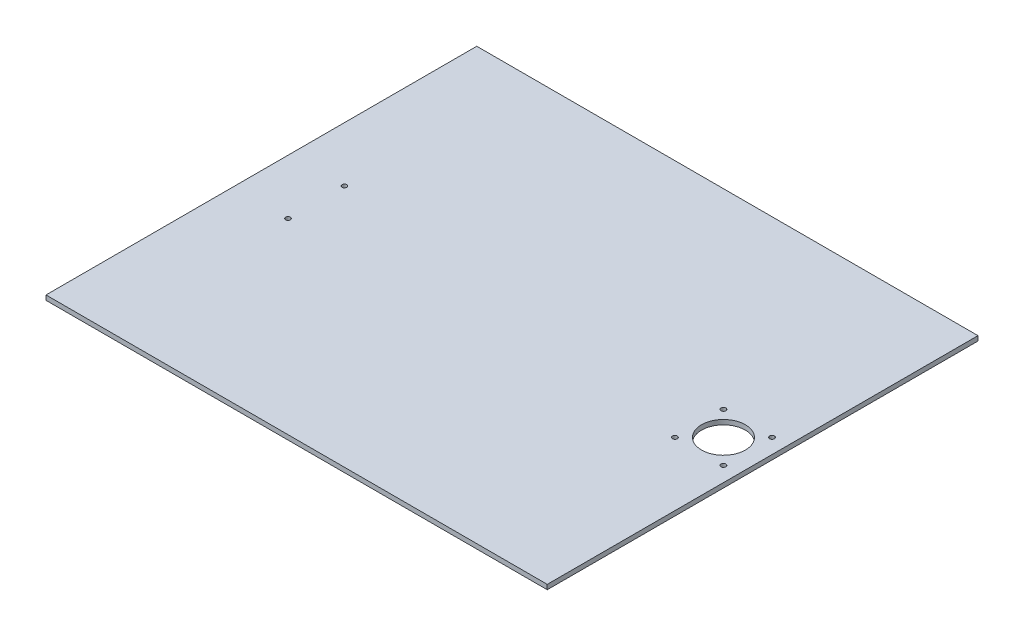
SolidWorks part; units mm, degrees
material "Acrílico (Impacto medio-alto)"
ref_plane "Alzado" through (0, 0, 0) normal (0, 0, 1) x (1, 0, 0)
ref_plane "Planta" through (0, 0, 0) normal (0, 1, 0) x (1, 0, 0)
ref_plane "Vista lateral" through (0, 0, 0) normal (1, 0, 0) x (0, 0, -1)
sketch "Sketch1" plane through (0, 0, 0) normal (0, 1, 0) x (1, 0, 0)
  line L1 (-160, -137.5) -> (160, -137.5)
  line L2 (-160, -137.5) -> (-160, 137.5)
  line L3 (-160, 137.5) -> (160, 137.5)
  line L4 (160, -137.5) -> (160, 137.5)
  line L5 (-160, -137.5) -> (160, 137.5) construction
  line L6 (-160, 137.5) -> (160, -137.5) construction
  point P0 (0, 0)
  dimension "D1" = 320
  dimension "D2" = 275
extrude "Boss-Extrude1" add sketch "Sketch1" along normal blind 3
sketch "Sketch2" plane through (0, 3, 0) normal (0, 1, 0) x (1, 0, 0)
  line L0 (0, 0) -> (160, 0) construction
  line L1 (160, -137.5) -> (160, 137.5) construction
  line L3 (119.5, -15.5) -> (150.5, -15.5)
  line L4 (119.5, -15.5) -> (119.5, 15.5)
  line L5 (119.5, 15.5) -> (150.5, 15.5)
  line L6 (150.5, -15.5) -> (150.5, 15.5)
  line L7 (119.5, -15.5) -> (150.5, 15.5) construction
  line L8 (119.5, 15.5) -> (150.5, -15.5) construction
  point P5 (135, 0)
  dimension "D1" = 31
  dimension "D2" = 31
  dimension "D3" = 25
sketch "Sketch3" plane through (0, 3, 0) normal (0, 1, 0) x (1, 0, 0)
  point P0 (150.5, 15.5)
  point P3 (150.5, -15.5)
  point P6 (119.5, -15.5)
  point P9 (119.5, 15.5)
hole_wizard "Taladro de margen para M2.51" positions "Sketch3" profile "Sketch4" hole size "M2.5" standard "ISO" end condition through all
sketch "Sketch4" plane through (150.5, 3, -15.5) normal (1, 0, 0) x (0, 0, 1)
  line L0 (0, 0) -> (0, 3)
  line L1 (0, 3) -> (1.55, 3)
  line L2 (1.55, 3) -> (1.55, 0)
  line L5 (1.55, 0) -> (0, 0)
  line L11 (0, -6.35) -> (0, 107.95) construction
  dimension "Diámetro de taladro hasta el siguiente" = 3.1
  dimension "Profundidad de taladro hasta el siguiente" = 3
sketch "Sketch6" plane through (0, 3, 0) normal (0, 1, 0) x (1, 0, 0)
  line L0 (0, 0) -> (-160, 0) construction
  line L1 (-160, 137.5) -> (-160, -137.5) construction
  line L2 (-125, 0) -> (-125, 18) construction
  line L3 (-125, 0) -> (-125, -18) construction
  circle A0 centre (-125, -18) radius 1.5
  circle A1 centre (-125, 18) radius 1.5
  dimension "D2" = 3
  dimension "D3" = 3
  dimension "D1" = 36
  dimension "D4" = 35
extrude "Cut-Extrude1" cut sketch "Sketch6" against normal through all
sketch "Sketch7" plane through (0, 3, 0) normal (0, 1, 0) x (1, 0, 0)
  line L0 (119.5, 15.5) -> (150.5, 15.5) construction
  line L1 (135, 15.5) -> (135, 0) construction
  line L2 (150.5, -15.5) -> (150.5, 15.5) construction
  circle A0 centre (135, 0) radius 14
  point P9 (0, 0)
  point P11 (150.5, 0)
  dimension "D1" = 28
extrude "Cut-Extrude2" cut sketch "Sketch7" against normal blind 10
